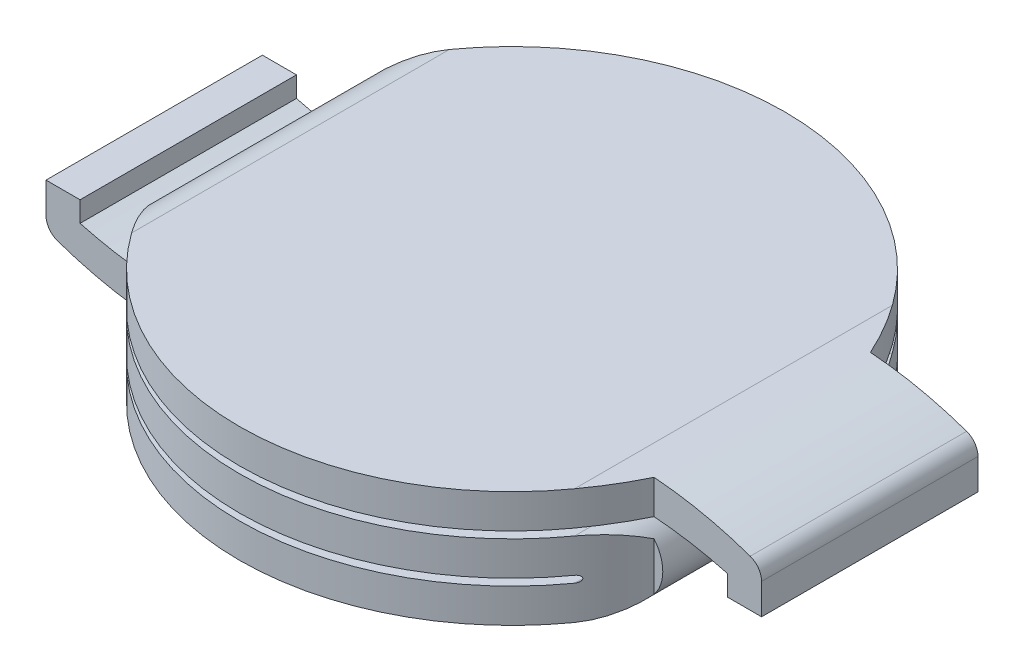
SolidWorks part; units mm, degrees
ref_plane "Front Plane" through (0, 0, 0) normal (0, 0, 1) x (1, 0, 0)
ref_plane "Top Plane" through (0, 0, 0) normal (0, 1, 0) x (1, 0, 0)
ref_plane "Right Plane" through (0, 0, 0) normal (1, 0, 0) x (0, 0, -1)
sketch "Sketch1" plane through (0, 0, 0) normal (0, 0, 1) x (1, 0, 0)
  line L0 (-6.5, 0) -> (6.5, 0)
  line L1 (-6.5, 1.2) -> (6.5, 1.2)
  line L2 (6.5, -1.2) -> (-6.5, -1.2)
  line L3 (6.5, -1.7) -> (-6.5, -1.7)
  line L4 (-6.5, 0.5) -> (6.5, 0.5)
  line L5 (-6.5, 0.7) -> (6.5, 0.7)
  line L6 (6.5, -0.7) -> (-6.5, -0.7)
  line L7 (-6.5, -0.5) -> (6.5, -0.5)
  line L8 (-6.5, 1.7) -> (6.5, 1.7)
  line L16 (-9.5, -0.3) -> (-9.5, 0.3)
  line L18 (-10.5, 0.3) -> (-10.5, -0.602)
  line L19 (-9.5, 0.3) -> (-10.5, 0.3)
  line L22 (10.5, 0.602) -> (10.5, -0.3)
  line L23 (10.5, -0.3) -> (9.5, -0.3)
  line L24 (9.5, 0.3) -> (9.5, -0.3)
  arc A0 (6.5, 0) -> (6.5, -1.2) centre (6.5, -0.6) cw
  arc A1 (-6.5, 0) -> (-6.5, 1.2) centre (-6.5, 0.6) cw
  arc A2 (6.5, 0.5) -> (6.5, -1.7) centre (6.5, -0.6) cw
  arc A3 (-6.5, 0.5) -> (-6.5, 0.7) centre (-6.5, 0.6) cw
  arc A4 (6.5, -0.5) -> (6.5, -0.7) centre (6.5, -0.6) cw
  arc A5 (-6.5, -0.5) -> (-6.5, 1.7) centre (-6.5, 0.6) cw
  arc A7 (6.5, 1.7) -> (10.166, 1.0736) centre (6.5, -9.3417) cw
  arc A8 (-6.5, -0.7) -> (-9.5, -0.3) centre (-6.5, 10.75) cw
  arc A9 (6.5, 0.7) -> (9.5, 0.3) centre (6.5, -10.75) cw
  arc A10 (-6.5, -1.7) -> (-10.166, -1.0736) centre (-6.5, 9.3417) cw
  arc A11 (-10.166, -1.0736) -> (-10.5, -0.602) centre (-10, -0.602) cw
  arc A12 (10.5, 0.602) -> (10.166, 1.0736) centre (10, 0.602) ccw
  point P4 (0, 0)
  point P9 (-10, 0.3)
  point P34 (10, -0.3)
  point P37 (10.766, 0.3)
  point P40 (10.3936, 0.3)
  point P42 (10.4282, 0.9053)
  point P43 (0, 0)
  point P44 (10, -0.3)
  point P45 (0, 0)
  point P46 (-10, 0.3)
  point P49 (-10.5, -0.95)
  point P52 (10.5, 0.95)
  dimension "D3" = 0.5
  dimension "D4" = 0.6
  dimension "D2" = 0.6
  dimension "D16" = 0.5
  dimension "D1" = 13
  dimension "D6" = 1
  dimension "D7" = 10
  dimension "D8" = 0.6
  dimension "D9" = 0.3
  dimension "D10" = 10
  dimension "D11" = 0.6
  dimension "D12" = 0.3
  dimension "D13" = 1
  dimension "D14" = 1.25
  dimension "D15" = 1.25
  dimension "D5" = 0.5
extrude "Boss-Extrude1" add sketch "Sketch1" along normal blind 16 contours L5 A9 A7 L8 A5 L7 A4 L6 A8 L3 A2 L4 A3 region at (0, -1.4873, 0)
sketch "Sketch2" plane through (0, 1.7, 0) normal (0, 1, 0) x (1, 0, 0)
  line L5 (-10.5, -16) -> (-10.5, 0) construction
  line L6 (-5.5, -11.175) -> (-10.5, -11.175)
  line L7 (0, 0) -> (0, -16) construction
  line L8 (5.5, -4.825) -> (10.5, -11.175) construction
  line L9 (5.5, -11.175) -> (10.5, -4.825) construction
  line L19 (-5.5, -11.175) -> (-5.5, -4.825)
  line L20 (-5.5, -4.825) -> (-10.5, -4.825)
  line L21 (-10.5, -11.175) -> (-10.5, -4.825)
  line L22 (-5.5, -11.175) -> (-10.5, -4.825) construction
  line L23 (-5.5, -4.825) -> (-10.5, -11.175) construction
  line L24 (10.5, -11.175) -> (10.5, -4.825)
  line L25 (5.5, -4.825) -> (10.5, -4.825)
  line L26 (5.5, -11.175) -> (5.5, -4.825)
  line L27 (5.5, -11.175) -> (10.5, -11.175)
  circle A0 centre (0, -8) radius 8
  circle A1 centre (0, -8) radius 16.202
  point P3 (-8, -8)
  point P4 (-8, -8)
  point P16 (8, -8)
  line M7 (6.5, 0) -> (-6.5, 0)
  line M8 (-6.5, 0) -> (-6.5, -16)
  line M9 (-6.5, -16) -> (6.5, -16)
  line M10 (6.5, -16) -> (6.5, 0)
  dimension "D1" = 16
  dimension "D2" = 6.35
extrude "Cut-Extrude2" cut sketch "Sketch2" against normal blind 16 and the other way blind 16 contours A1 A0 L20 L25 L24 L27 M10 M9 M8 M7 | A0 M8 M9 | A0 M9 M10 | A0 M7 M8 | A0 M10 M7 region at (-4.9505, 1.7, 15.0489) region at (-4.9505, 1.7, 0.9511) region at (4.9505, 1.7, 15.0489) region at (4.9505, 1.7, 0.9511) region at (-15.7437, 1.7, 8)
